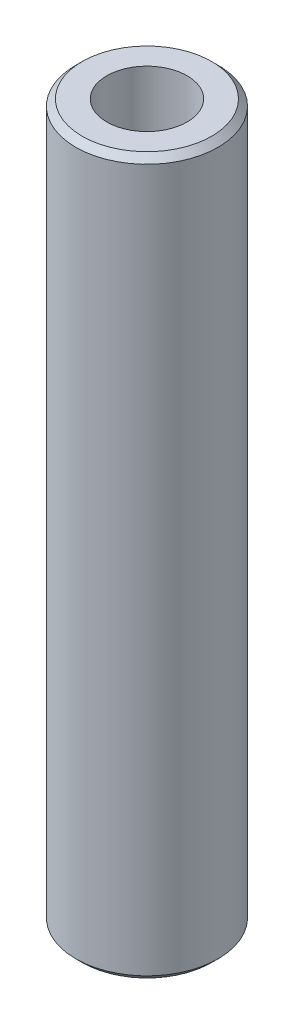
SolidWorks part; units mm, degrees
ref_plane "Front Plane" through (0, 0, 0) normal (0, 0, 1) x (1, 0, 0)
ref_plane "Top Plane" through (0, 0, 0) normal (0, 1, 0) x (1, 0, 0)
ref_plane "Right Plane" through (0, 0, 0) normal (1, 0, 0) x (0, 0, -1)
sketch "Sketch1" plane through (0, 0, 0) normal (0, 1, 0) x (1, 0, 0)
  circle A0 centre (0, 0) radius 37.5
  dimension "SHAFT_OD" = 75
extrude "Boss-Extrude1" add sketch "Sketch1" along normal blind 377.2275
sketch "Sketch2" plane through (0, 0, 0) normal (0, 1, 0) x (1, 0, 0)
  circle A0 centre (0, 0) radius 21.1526
  dimension "BORE_D" = 42.3053
extrude "Cut-Extrude1" cut sketch "Sketch2" along normal through all
chamfer "Chamfer1" distance 3.3669 angle 45 2 edges at (0, 377.2275, 37.5) (0, 0, 37.5)
